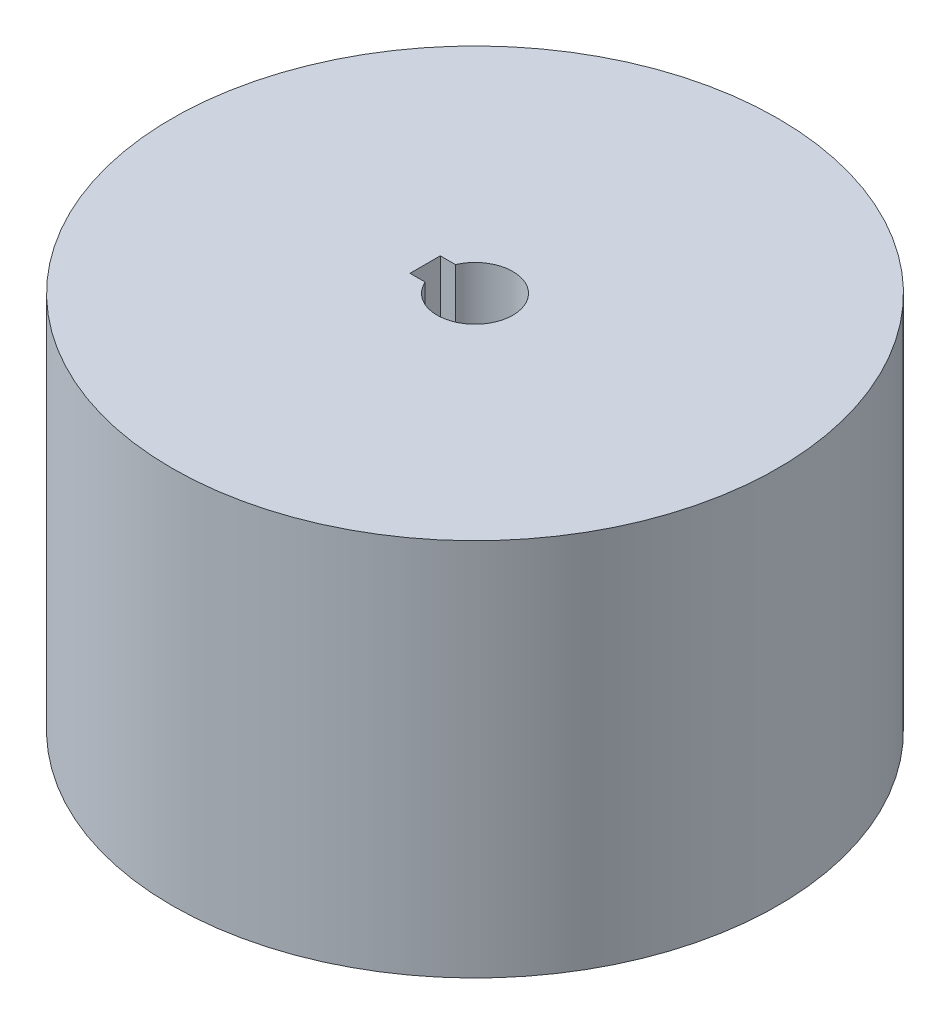
SolidWorks part; units mm, degrees
ref_plane "前视基准面" through (0, 0, 0) normal (0, 0, 1) x (1, 0, 0)
ref_plane "上视基准面" through (0, 0, 0) normal (0, 1, 0) x (1, 0, 0)
ref_plane "右视基准面" through (0, 0, 0) normal (1, 0, 0) x (0, 0, -1)
other "Configuration Table"
sketch "草图1" plane through (0, 0, 0) normal (0, 1, 0) x (1, 0, 0)
  circle A0 centre (0, 0) radius 40
  circle A1 centre (0, 0) radius 5
  dimension "D1" = 80
  dimension "D2" = 10
extrude "凸台-拉伸1" add sketch "草图1" along normal blind 50
sketch "草图2" plane through (0, 50, 0) normal (0, 1, 0) x (1, 0, 0)
  line L1 (-6.5826, 2) -> (-4.5826, 2)
  line L2 (-6.5826, 2) -> (-6.5826, -2)
  line L3 (-6.5826, -2) -> (-4.5826, -2)
  line L4 (-4.5826, 2) -> (-4.5826, -2)
  line L5 (-6.5826, 2) -> (-4.5826, -2) construction
  line L6 (-6.5826, -2) -> (-4.5826, 2) construction
  circle A1 centre (0, 0) radius 5 construction
  point P0 (-5.5826, 0)
  point P5 (0, 0)
  point P7 (0, 0)
  point P8 (-1.5833, 4.7427)
  point P10 (-2.0641, 4.0722)
  dimension "D1" = 2
  dimension "D2" = 4
extrude "切除-拉伸1" cut sketch "草图2" against normal blind 50
